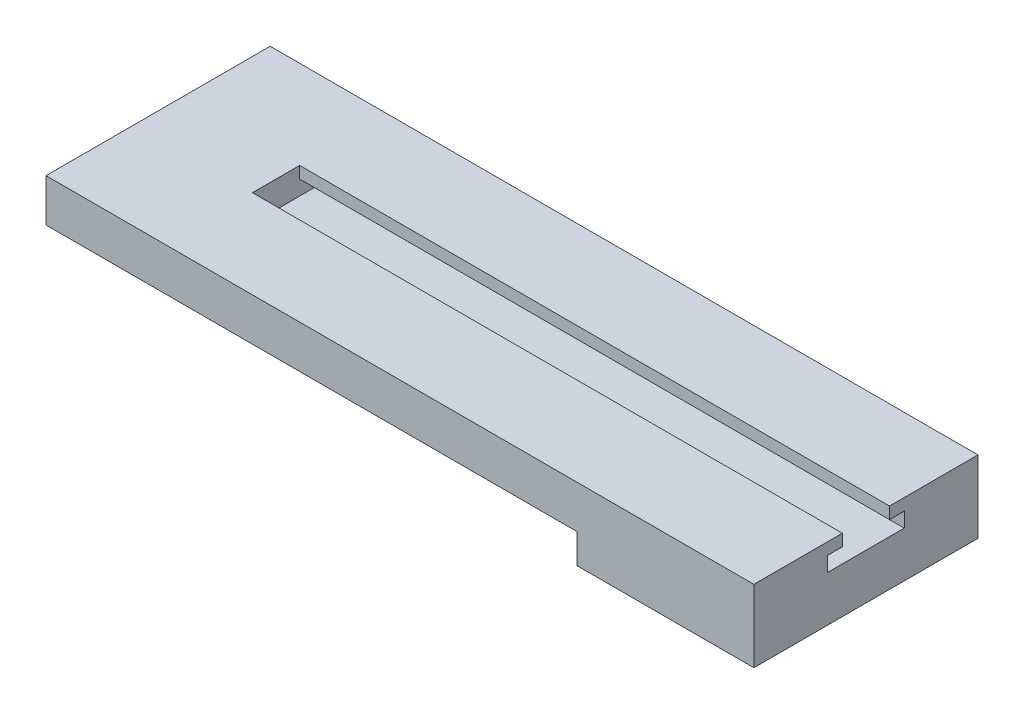
SolidWorks part; units mm, degrees
ref_plane "Front Plane" through (0, 0, 0) normal (0, 0, 1) x (1, 0, 0)
ref_plane "Top Plane" through (0, 0, 0) normal (0, 1, 0) x (1, 0, 0)
ref_plane "Right Plane" through (0, 0, 0) normal (1, 0, 0) x (0, 0, -1)
sketch "Sketch1" plane through (0, 0, 0) normal (0, 1, 0) x (1, 0, 0)
  line L0 (0, 0) -> (200, 0)
  line L1 (0, 0) -> (0, -16)
  line L2 (0, -16) -> (200, -16)
  line L3 (200, -16) -> (200, -46)
  line L4 (200, -46) -> (-40, -46)
  line L5 (-40, -46) -> (-40, 30)
  line L6 (-40, 30) -> (200, 30)
  line L7 (200, 30) -> (200, 0)
  dimension "D1" = 200
  dimension "D2" = 16
  dimension "D3" = 30
  dimension "D4" = 240
  dimension "D5" = 76
extrude "Boss-Extrude1" add sketch "Sketch1" along normal blind 4
sketch "Sketch2" plane through (0, 0, 0) normal (0, 1, 0) x (1, 0, 0)
  line L0 (209.7303, -8) -> (-59.5425, -8) construction
  line L1 (200, -8) -> (200, 5) construction
  line L2 (200, 5) -> (0, 5)
  line L3 (0, 5) -> (0, -21)
  line L4 (200, 5) -> (200, 30)
  line L5 (200, 30) -> (-40, 30)
  line L6 (-40, 30) -> (-40, -46)
  line L7 (-40, 30) -> (-40, -46) construction
  line L8 (200, -21) -> (200, -46)
  line L9 (200, -21) -> (0, -21)
  line L10 (200, -46) -> (-40, -46)
  point P18 (0, -8)
  point P19 (-40, -8)
  dimension "D1" = 13
extrude "Boss-Extrude2" add sketch "Sketch2" against normal blind 5
sketch "Sketch3" plane through (0, 0, 0) normal (0, 1, 0) x (1, 0, 0)
  line L0 (-40, 30) -> (200, 30)
  line L1 (200, 30) -> (200, -46)
  line L2 (200, -46) -> (-40, -46)
  line L3 (-40, -46) -> (-40, 30)
extrude "Boss-Extrude3" add sketch "Sketch3" against normal blind 5.5 from offset 5 offset against normal yes
sketch "Sketch4" plane through (0, 0, 0) normal (0, 1, 0) x (1, 0, 0)
  line L0 (200, 30) -> (200, -46)
  line L1 (200, -46) -> (140, -46)
  line L2 (-40, -46) -> (200, -46) construction
  line L3 (140, -46) -> (140, 30)
  line L4 (200, 30) -> (-40, 30) construction
  line L5 (140, 30) -> (200, 30)
  dimension "D1" = 60
extrude "Boss-Extrude4" add sketch "Sketch4" against normal blind 10 from offset 10.5 contours L5 L0 L1 L3 offset against normal yes
sketch "Sketch5" plane through (0, 0, 0) normal (0, 1, 0) x (1, 0, 0)
  line L0 (170, -46) -> (170, 30) construction
  line L1 (200, -46) -> (140, -46) construction
  line L2 (140, 30) -> (200, 30) construction
  line L3 (200, -8) -> (140, -8) construction
  line L4 (200, 30) -> (200, -46) construction
  line L5 (140, -46) -> (140, 30) construction
  circle A0 centre (170, -8) radius 10.5
  dimension "D1" = 21
extrude "Cut-Extrude1" cut sketch "Sketch5" along normal blind 4 from offset 20.5 offset against normal yes
